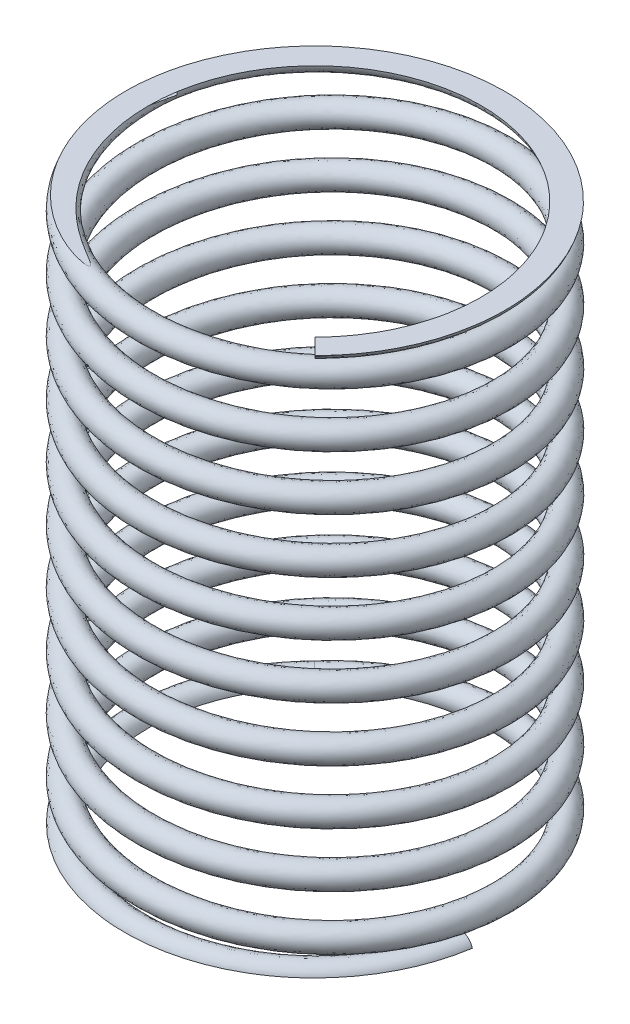
SolidWorks part; units mm, degrees
material "Alloy Steel (SS)"
ref_plane "Front Plane" through (0, 0, 0) normal (0, 0, 1) x (1, 0, 0)
ref_plane "Top Plane" through (0, 0, 0) normal (0, 1, 0) x (1, 0, 0)
ref_plane "Right Plane" through (0, 0, 0) normal (1, 0, 0) x (0, 0, -1)
sketch "Sketch1" plane through (0, 0, 0) normal (0, 1, 0) x (1, 0, 0)
  circle A0 centre (0, 0) radius 23.775
  dimension "D1" = 47.55
curve "Helix/Spiral1" pitch 7.2727 height 72 turns 9.9
sweep "Sweep1" add path "Helix/Spiral1" circular profile diameter 3.25 parameters "D3"=3.25
sketch "Sketch15" plane through (0, 0, 0) normal (0, 1, 0) x (1, 0, 0)
  circle A0 centre (0, 0) radius 23.775
  dimension "D1" = 47.55
curve "Helix/Spiral2" pitch 1 height 0.6 turns 0.6
sweep "Sweep2" add path "Helix/Spiral2" parameters "D3"=3.25
ref_plane "Plane2" through (0, 72, 0) normal (0, 1, 0) x (1, 0, 0)
sketch "Sketch32" plane through (0, 72, 0) normal (0, 1, 0) x (1, 0, 0)
  circle A0 centre (0, 0) radius 23.775
  dimension "D1" = 47.55
curve "Helix/Spiral3" pitch 1 height 0.6 turns 0.6
sweep "Sweep3" add path "Helix/Spiral3" circular profile diameter 3.25 parameters "D3"=3.25
sketch "Sketch46" plane through (0, 0, 0) normal (0, 0, 1) x (1, 0, 0)
  line L0 (0, 0) -> (0, 72) construction
  line L1 (-30, 0) -> (30, 0)
  line L2 (-30, 0) -> (-30, -10)
  line L3 (-30, -10) -> (30, -10)
  line L4 (30, 0) -> (30, -10)
  line L5 (-30, 72) -> (30, 72)
  line L6 (-30, 72) -> (-30, 82)
  line L7 (-30, 82) -> (30, 82)
  line L8 (30, 72) -> (30, 82)
  point P8 (0, 0)
  point P10 (0, 72)
  dimension "D1" = 72
  dimension "D2" = 10
  dimension "D3" = 60
extrude "Cut-Extrude1" cut sketch "Sketch46" against normal through all both and the other way through all
